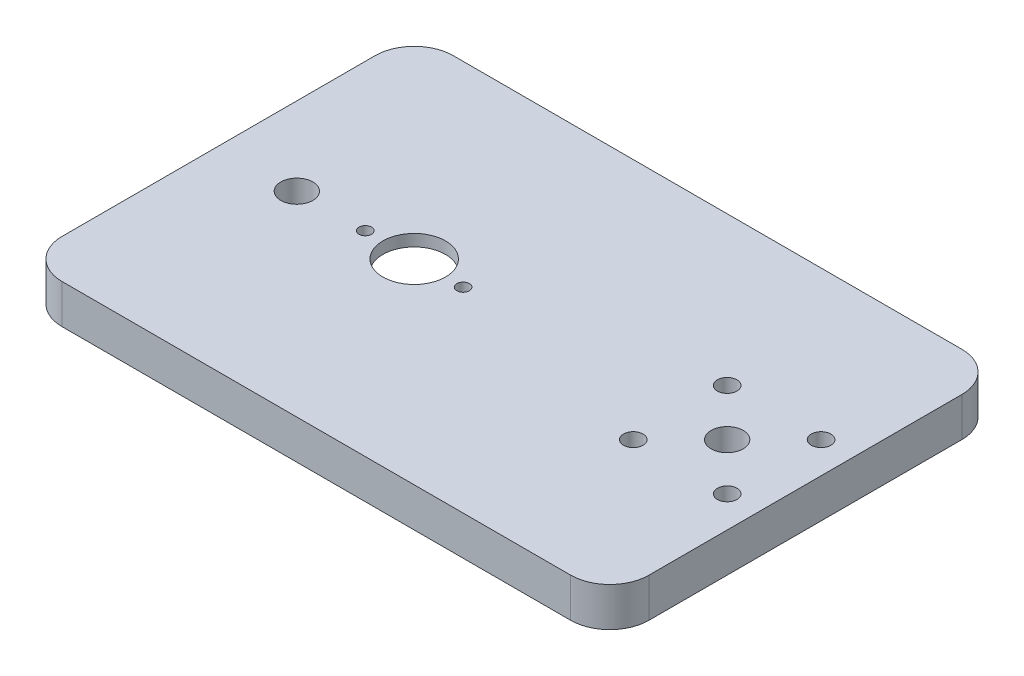
SolidWorks part; units mm, degrees
ref_plane "正面" through (0, 0, 0) normal (0, 0, 1) x (1, 0, 0)
ref_plane "平面" through (0, 0, 0) normal (0, 1, 0) x (1, 0, 0)
ref_plane "右側面" through (0, 0, 0) normal (1, 0, 0) x (0, 0, -1)
sketch "ｽｹｯﾁ1" plane through (0, 0, 0) normal (0, 1, 0) x (1, 0, 0)
  line L1 (-65, -50) -> (65, -50)
  line L2 (-75, -40) -> (-75, 40)
  line L3 (-65, 50) -> (65, 50)
  line L4 (75, -40) -> (75, 40)
  line L5 (-75, -50) -> (75, 50) construction
  line L6 (-75, 50) -> (75, -50) construction
  circle A0 centre (55, 0) radius 4.1
  circle A1 centre (43, 12) radius 2.5
  circle A2 centre (67, 12) radius 2.5
  circle A3 centre (67, -12) radius 2.5
  circle A4 centre (43, -12) radius 2.5
  arc A5 (65, 50) -> (75, 40) centre (65, 40) cw
  arc A6 (65, -50) -> (75, -40) centre (65, -40) ccw
  arc A7 (-65, -50) -> (-75, -40) centre (-65, -40) cw
  arc A8 (-75, 40) -> (-65, 50) centre (-65, 40) cw
  circle A9 centre (-55, 0) radius 4.1
  point P0 (0, 0)
  point P16 (0, 0)
  dimension "D3" = 8.2
  dimension "D9" = 5
  dimension "D10" = 10
  dimension "D11" = 8.2
  dimension "D1" = 150
  dimension "D2" = 100
  dimension "D4" = 20
  dimension "D5" = 24
  dimension "D6" = 24
  dimension "D7" = 12
  dimension "D8" = 12
  dimension "D12" = 20
extrude "ﾎﾞｽ - 押し出し1" add sketch "ｽｹｯﾁ1" along normal blind 10
sketch "ｽｹｯﾁ2" plane through (0, 0, 0) normal (0, 1, 0) x (1, 0, 0)
  circle A0 centre (-25, 0) radius 19
  circle A2 centre (-55, 0) radius 4.1 construction
  point P2 (0, 0)
  point P7 (0, 0)
  dimension "D1" = 38
  dimension "D2" = 30
extrude "ｶｯﾄ - 押し出し1" cut sketch "ｽｹｯﾁ2" along normal offset from surface (7 mm away) 3 up to face at (0, 10, 0)
sketch "ｽｹｯﾁ3" plane through (0, 7, 0) normal (0, -1, 0) x (1, 0, 0)
  circle A0 centre (-25, 0) radius 8
  circle A1 centre (-37.5, 0) radius 1.6
  circle A2 centre (-12.5, 0) radius 1.6
  point P7 (0, 0)
  point P9 (0, 0)
  dimension "D1" = 16
  dimension "D4" = 3.2
  dimension "D2" = 25
  dimension "D3" = 12.5
extrude "ｶｯﾄ - 押し出し2" cut sketch "ｽｹｯﾁ3" against normal through all and the other way through all
